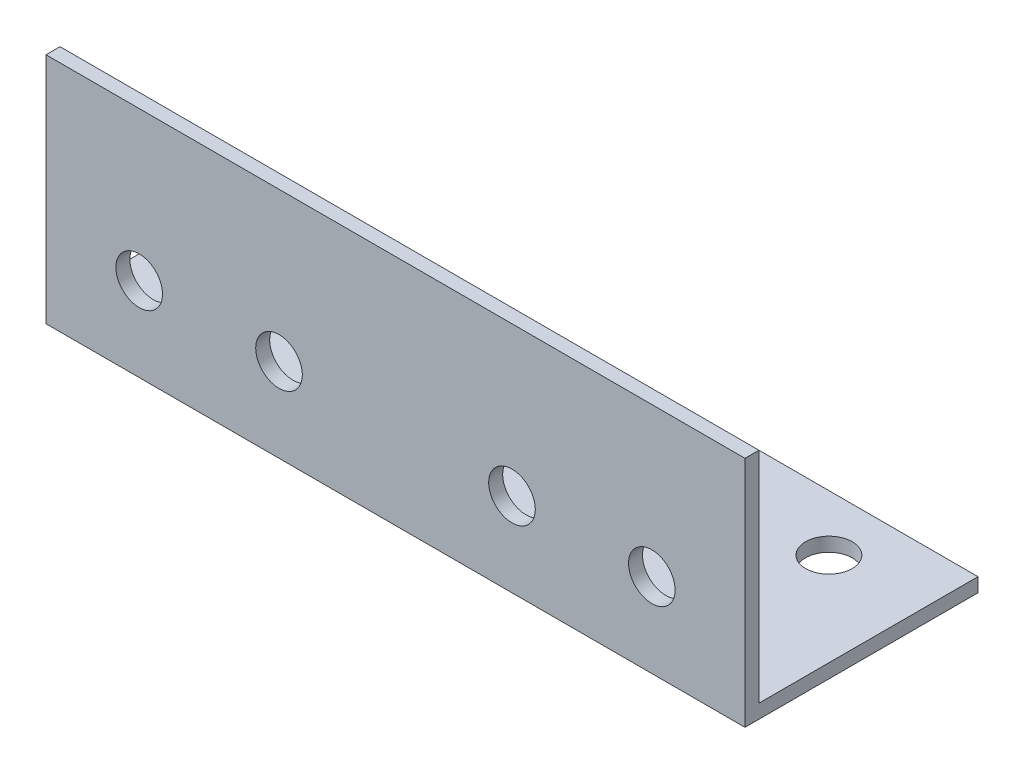
SolidWorks part; units mm, degrees
ref_plane "Спереди" through (0, 0, 0) normal (0, 0, 1) x (1, 0, 0)
ref_plane "Сверху" through (0, 0, 0) normal (0, 1, 0) x (1, 0, 0)
ref_plane "Справа" through (0, 0, 0) normal (1, 0, 0) x (0, 0, -1)
sketch "Эскиз1" plane through (0, 0, 0) normal (1, 0, 0) x (0, 0, -1)
  line L0 (0, 0) -> (0, 50)
  line L1 (0, 0) -> (50, 0)
extrude "Вытянуть-Тонкостенный1" add sketch "Эскиз1" along normal blind 150 thin thin type one direction reverse wall 3
sketch "Эскиз2" plane through (0, 0, 0) normal (0, -1, 0) x (1, 0, 0)
  line L0 (75, -58.7293) -> (75, -21.2393) construction
  circle A0 centre (130, -38) radius 5
  circle A1 centre (100, -38) radius 5
  circle A2 centre (50, -38) radius 5
  circle A3 centre (20, -38) radius 5
  dimension "D1" = 2
extrude "Вырез-Вытянуть1" cut sketch "Эскиз2" against normal through all
sketch "Эскиз3" plane through (0, 0, 0) normal (0, 0, 1) x (1, 0, 0)
  line L0 (75, 50) -> (75, 0) construction
  line L1 (150, 50) -> (0, 50) construction
  circle A0 centre (130, 18) radius 5
  circle A1 centre (100, 18) radius 5
  circle A2 centre (50, 18) radius 5
  circle A3 centre (20, 18) radius 5
  dimension "D1" = 2
extrude "Вырез-Вытянуть3" cut sketch "Эскиз3" against normal through all
